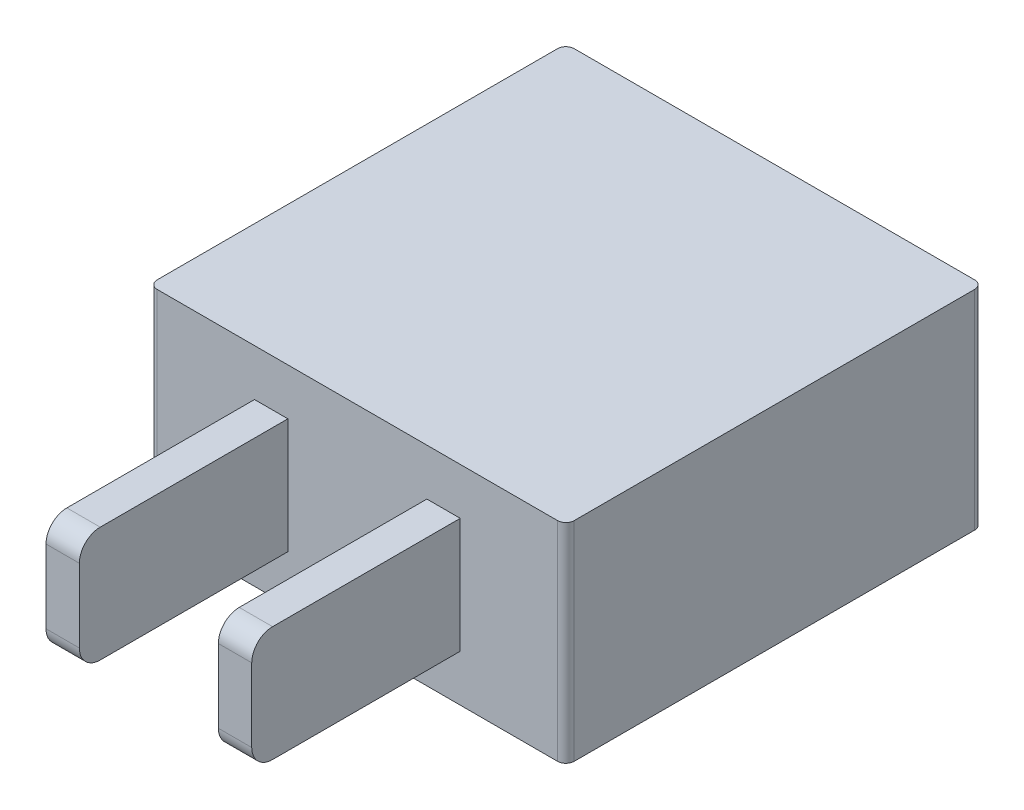
SolidWorks part; units mm, degrees
ref_plane "Front Plane" through (0, 0, 0) normal (0, 0, 1) x (1, 0, 0)
ref_plane "Top Plane" through (0, 0, 0) normal (0, 1, 0) x (1, 0, 0)
ref_plane "Right Plane" through (0, 0, 0) normal (1, 0, 0) x (0, 0, -1)
sketch "Sketch1" plane through (0, 0, 0) normal (0, 1, 0) x (1, 0, 0)
  line L1 (-6.35, -6.35) -> (6.35, -6.35)
  line L2 (-6.35, -6.35) -> (-6.35, 6.35)
  line L3 (-6.35, 6.35) -> (6.35, 6.35)
  line L4 (6.35, -6.35) -> (6.35, 6.35)
  line L5 (-6.35, -6.35) -> (6.35, 6.35) construction
  line L6 (-6.35, 6.35) -> (6.35, -6.35) construction
  point P0 (0, 0)
  dimension "D1" = 12.7
extrude "Boss-Extrude1" add sketch "Sketch1" along normal blind 6.35
sketch "Sketch2" plane through (0, 0, 6.35) normal (0, 0, 1) x (1, 0, 0)
  line L1 (-6.35, 6.35) -> (6.35, 6.35)
  line L2 (-6.35, 6.35) -> (-6.35, 0)
  line L3 (-6.35, 0) -> (6.35, 0)
  line L4 (6.35, 6.35) -> (6.35, 0)
  line L5 (-6.35, 6.35) -> (6.35, 0) construction
  line L6 (-6.35, 0) -> (6.35, 6.35) construction
  line L7 (-2.1167, 1.4224) -> (2.1167, 1.4224) construction
  line L8 (-2.1167, 1.4224) -> (-2.1167, 4.9276) construction
  line L9 (-2.1167, 4.9276) -> (2.1167, 4.9276) construction
  line L10 (2.1167, 1.4224) -> (2.1167, 4.9276) construction
  line L11 (-2.1167, 1.4224) -> (2.1167, 4.9276) construction
  line L12 (-2.1167, 4.9276) -> (2.1167, 1.4224) construction
  line L13 (2.1167, 4.9276) -> (3.1327, 4.9276)
  line L14 (2.1167, 4.9276) -> (2.1167, 1.4224)
  line L15 (2.1167, 1.4224) -> (3.1327, 1.4224)
  line L16 (3.1327, 4.9276) -> (3.1327, 1.4224)
  line L17 (2.1167, 4.9276) -> (3.1327, 1.4224) construction
  line L18 (2.1167, 1.4224) -> (3.1327, 4.9276) construction
  line L19 (-2.1167, 1.4224) -> (-3.1327, 1.4224)
  line L20 (-2.1167, 1.4224) -> (-2.1167, 4.9276)
  line L21 (-2.1167, 4.9276) -> (-3.1327, 4.9276)
  line L22 (-3.1327, 1.4224) -> (-3.1327, 4.9276)
  line L23 (-2.1167, 1.4224) -> (-3.1327, 4.9276) construction
  line L24 (-2.1167, 4.9276) -> (-3.1327, 1.4224) construction
  point P4 (0, 3.175)
  point P7 (0, 3.175)
  point P14 (2.6247, 3.175)
  point P17 (-2.6247, 3.175)
  dimension "D1" = 4.2333
  dimension "D2" = 3.5052
  dimension "D3" = 1.016
extrude "Boss-Extrude2" add sketch "Sketch2" along normal blind 6.35 contours L22 L19 L20 L21 | L16 L13 L14 L15 | L20 L19 L22 L21 | L14 L13 L16 L15 region at (2.6247, 3.175, 6.35) region at (-2.6247, 3.175, 6.35)
fillet "Fillet1" radius 0.635 4 edges at (2.6247, 4.9276, 12.7) (2.6247, 1.4224, 12.7) (-2.6247, 1.4224, 12.7) (-2.6247, 4.9276, 12.7)
fillet "Fillet2" radius 0.254 4 edges at (-6.35, 3.175, -6.35) (6.35, 3.175, -6.35) (6.35, 3.175, 6.35) (-6.35, 3.175, 6.35)
